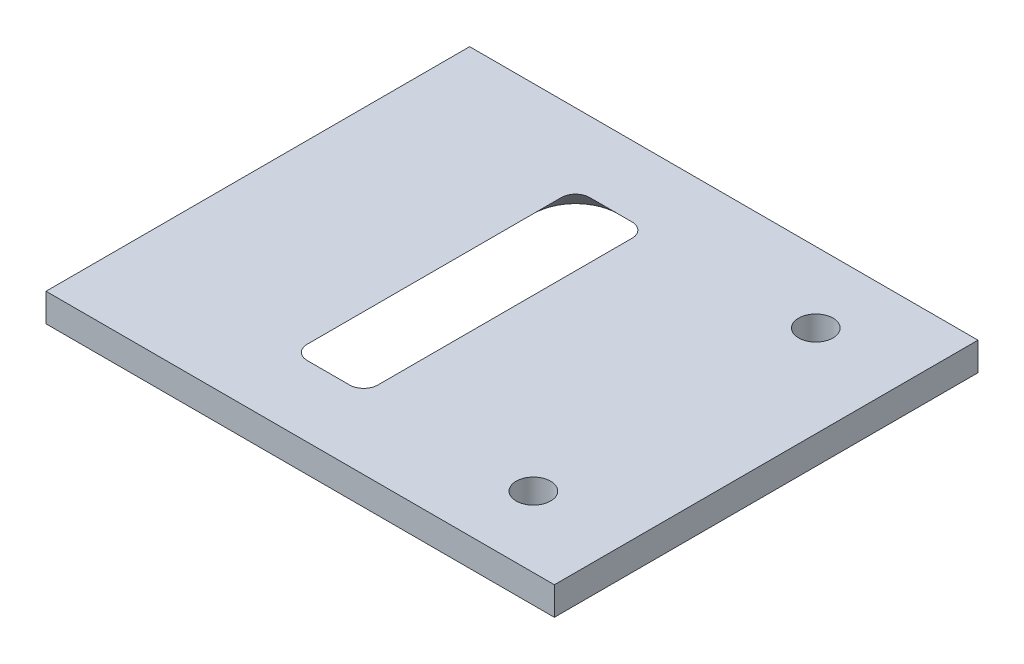
SolidWorks part; units mm, degrees
material "6061-T4 (SS)"
ref_plane "Front Plane" through (0, 0, 0) normal (0, 0, 1) x (1, 0, 0)
ref_plane "Top Plane" through (0, 0, 0) normal (0, 1, 0) x (1, 0, 0)
ref_plane "Right Plane" through (0, 0, 0) normal (1, 0, 0) x (0, 0, -1)
sketch "Sketch2" plane through (0, 0, 0) normal (0, 1, 0) x (1, 0, 0)
  line L0 (3, 0) -> (0, 0) construction
  line L5 (-15, 15) -> (21, 15)
  line L6 (-15, 15) -> (-15, -15)
  line L7 (-15, -15) -> (21, -15)
  line L8 (21, 15) -> (21, -15)
  line L9 (-15, 15) -> (21, -15) construction
  line L10 (-15, -15) -> (21, 15) construction
  dimension "D1" = 36
  dimension "D2" = 30
  dimension "D3" = 3
extrude "Boss-Extrude1" add sketch "Sketch2" along normal blind 2
sketch "Sketch4" plane through (0, 2, 0) normal (0, 1, 0) x (1, 0, 0)
  line L1 (1.5, -10) -> (-1.5, -10)
  line L2 (2.5, -9) -> (2.5, 9)
  line L3 (1.5, 10) -> (-1.5, 10)
  line L4 (-2.5, -9) -> (-2.5, 9)
  line L5 (2.5, -10) -> (-2.5, 10) construction
  line L6 (2.5, 10) -> (-2.5, -10) construction
  arc A0 (1.5, -10) -> (2.5, -9) centre (1.5, -9) ccw
  arc A1 (2.5, 9) -> (1.5, 10) centre (1.5, 9) ccw
  arc A2 (-1.5, 10) -> (-2.5, 9) centre (-1.5, 9) ccw
  arc A3 (-1.5, -10) -> (-2.5, -9) centre (-1.5, -9) cw
  point P0 (0, 0)
  dimension "D3" = 1
  dimension "D1" = 20
  dimension "D2" = 5
extrude "Cut-Extrude4" cut sketch "Sketch4" against normal through all draft 45 draft outward yes
sketch3d "3DSketch1"
  line L0 (0, 2, 0) -> (0, 20.7837, 0) construction
hole_wizard "#2 Clearance Hole1" positions "Sketch7" profile "Sketch6" hole size "#2" standard "ANSI Inch" end condition through all
sketch "Sketch7" plane through (0, 0, 0) normal (0, -1, 0) x (-1, 0, 0)
  circle A0 centre (-14.5138, 10) radius 0.889 construction
  circle A1 centre (-14.5138, -10) radius 0.889 construction
  point P0 (-14.5138, -10)
  point P2 (-14.5138, 10)
  point P8 (0, 0)
  point P11 (0, 0)
sketch "Sketch6" plane through (14.5138, 0, 10) normal (1, 0, 0) x (0, 0, -1)
  line L0 (0, 0) -> (0, 2)
  line L1 (0, 2) -> (1.2192, 2)
  line L2 (1.2192, 2) -> (1.2192, 0)
  line L5 (1.2192, 0) -> (0, 0)
  line L11 (0, -6.35) -> (0, 107.95) construction
  dimension "Thru Hole Dia." = 2.4384
  dimension "Thru Hole Depth" = 2
